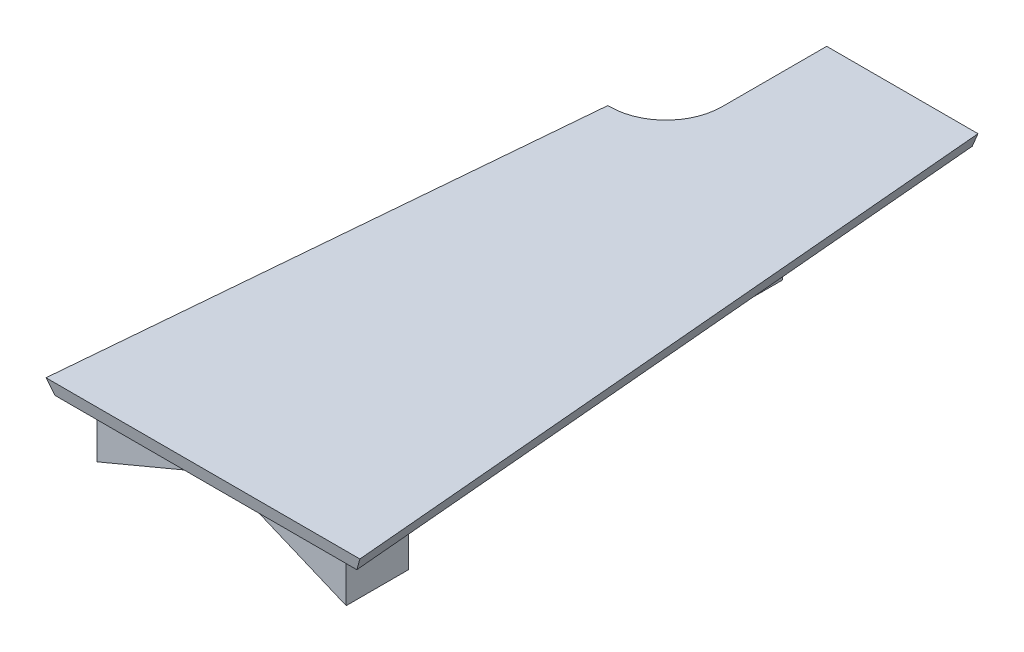
SolidWorks part; units mm, degrees
ref_plane "Ebene vorne" through (0, 0, 0) normal (0, 0, 1) x (1, 0, 0)
ref_plane "Ebene oben" through (0, 0, 0) normal (0, 1, 0) x (1, 0, 0)
ref_plane "Ebene rechts" through (0, 0, 0) normal (1, 0, 0) x (0, 0, -1)
sketch "Skizze1" plane through (0, 0, 0) normal (0, 1, 0) x (1, 0, 0)
  line L1 (-28.5, -61.5) -> (28.5, -61.5)
  line L2 (-28.5, -61.5) -> (-28.5, 61.5)
  line L3 (-28.5, 61.5) -> (28.5, 61.5)
  line L4 (28.5, -61.5) -> (28.5, 61.5)
  line L5 (-28.5, -61.5) -> (28.5, 61.5) construction
  line L6 (-28.5, 61.5) -> (28.5, -61.5) construction
  point P0 (0, 0)
  dimension "D1" = 57
  dimension "D2" = 123
extrude "Aufsatz-Linear austragen1" add sketch "Skizze1" along normal blind 2.5
sketch "Skizze2" plane through (28.5, 0, 0) normal (1, 0, 0) x (0, 0, -1)
  line L0 (-61.5, 2.5) -> (-61.5, 0)
  line L1 (55, 0) -> (-55, 0) construction
  line L2 (-61.5, 2.5) -> (-61.5, 0) construction
  line L3 (-61.5, 0) -> (-60.9686, 0)
  line L4 (-60.9686, 0) -> (-61.5, 2.5)
  dimension "D1" = 102
extrude "Schnitt-Linear austragen1" cut sketch "Skizze2" against normal through all
sketch "Skizze3" plane through (0, 2.5, 0) normal (0, 1, 0) x (1, 0, 0)
  line L0 (-28.5, -61.5) -> (-17.7389, 61.5)
  line L1 (28.5, 61.5) -> (-28.5, 61.5) construction
  line L2 (-17.7389, 61.5) -> (-28.5, 61.5)
  line L3 (-28.5, 61.5) -> (-28.5, -61.5)
  line L4 (28.5, -61.5) -> (17.7389, 61.5)
  line L5 (17.7389, 61.5) -> (28.5, 61.5)
  line L6 (28.5, 61.5) -> (28.5, -61.5)
  dimension "D1" = 95
  dimension "D2" = 95
extrude "Schnitt-Linear austragen2" cut sketch "Skizze3" against normal through all
ref_axis "Achse1" through (23.1194, 2.5, 0) along (0, -1, 0)
ref_plane "Ebene1" through (0.1756, 0, 2.0073) normal (0.0872, 0, 0.9962) x (0, -1, 0)
sketch "Skizze5" plane through (0.1756, 0, 2.0073) normal (0.0872, 0, 0.9962) x (0, -1, 0)
  line L0 (0.0086, 23.0315) -> (-2.5, 23.0315)
  line L1 (-2.5, 23.0315) -> (0, 23.0315) construction
  line L5 (0.0086, 23.0315) -> (0, 21.9959)
  line L6 (0, -33.659) -> (0, 23.0315) construction
  line L7 (0, 21.9959) -> (-2.5, 23.0315)
  line L8 (-2.5, -33.7516) -> (-2.5, 23.0315) construction
  dimension "D1" = 67.5
extrude "Schnitt-Linear austragen3" cut sketch "Skizze5" against normal through all and the other way through all
ref_axis "Achse2" through (-23.0962, -8.4274, -0.2657) along (0, 1, 0)
ref_plane "Ebene2" through (-0.1524, 0, 1.7416) normal (-0.0872, 0, 0.9962) x (0, 1, 0)
sketch "Skizze6" plane through (-0.1524, 0, 1.7416) normal (-0.0872, 0, 0.9962) x (0, 1, 0)
  line L1 (2.5, 23.0315) -> (0, 21.9959)
  line L2 (0, -55) -> (0, 55) construction
  line L3 (0, 21.9959) -> (0, 23.0315)
  line L4 (0, 23.0315) -> (2.5, 23.0315)
  line L5 (2.5, 23.0315) -> (2.5, -33.7516) construction
  dimension "D1" = 67.5
extrude "Schnitt-Linear austragen4" cut sketch "Skizze6" against normal through all and the other way through all
sketch "Skizze9" plane through (0, 0, 0) normal (0, -1, 0) x (1, 0, 0)
  line L6 (0, -61.5) -> (0, 60.9686) construction
  line L11 (16.6994, -61.5) -> (-16.6994, -61.5) construction
  line L12 (-27.414, 60.9686) -> (27.414, 60.9686) construction
  line L13 (0, 52.4686) -> (-26.6704, 52.4686) construction
  line L14 (-16.6994, -61.5) -> (-27.414, 60.9686) construction
  line L15 (-26.6704, 52.4686) -> (26.6704, 52.4686) construction
  line L16 (16.6994, -61.5) -> (27.414, 60.9686) construction
  line L17 (0, -19.5) -> (-20.3739, -19.5) construction
  line L18 (-20.3739, -19.5) -> (20.3739, -19.5) construction
  line L20 (22.6207, 58.1089) -> (-22.6207, 58.1089)
  line L21 (22.6207, 58.1089) -> (22.6207, 46.8283)
  line L22 (22.6207, 46.8283) -> (-22.6207, 46.8283)
  line L23 (-22.6207, 58.1089) -> (-22.6207, 46.8283)
  line L24 (22.6207, 58.1089) -> (-22.6207, 46.8283) construction
  line L25 (22.6207, 46.8283) -> (-22.6207, 58.1089) construction
  dimension "D1" = 42
  dimension "D2" = 8.5
extrude "Aufsatz-Linear austragen2" add sketch "Skizze9" along normal blind 13 contours L21 L20 L23 L22
sketch "Skizze11" plane through (0, 0, 46.8283) normal (0, 0, -1) x (-1, 0, 0)
  line L0 (-22.6207, -9.484) -> (0, 0)
  line L1 (-22.6207, -13) -> (-22.6207, 0) construction
  line L2 (-22.6207, 0) -> (22.6207, 0) construction
  line L3 (0, 0) -> (22.6207, -9.484)
  line L4 (22.6207, -13) -> (22.6207, 0) construction
  line L5 (22.6207, -9.484) -> (22.6207, -13)
  line L6 (22.6207, -13) -> (-22.6207, -13)
  line L7 (-22.6207, -13) -> (-22.6207, -9.484)
extrude "Schnitt-Linear austragen5" cut sketch "Skizze11" against normal blind 20
sketch "Skizze12" plane through (0, 0, 0) normal (0, -1, 0) x (1, 0, 0)
  line L0 (0, -61.5) -> (0, -2.1503) construction
  line L5 (16.6994, -61.5) -> (-16.6994, -61.5) construction
  line L6 (-20.3739, -19.5) -> (20.3739, -19.5) construction
  line L12 (-16.6994, -61.5) -> (-27.414, 60.9686) construction
  line L13 (16.6994, -61.5) -> (27.414, 60.9686) construction
  line L15 (18.0118, -15.2638) -> (-18.0118, -15.2638)
  line L16 (18.0118, -15.2638) -> (18.0118, -25.7362)
  line L17 (18.0118, -25.7362) -> (-18.0118, -25.7362)
  line L18 (-18.0118, -15.2638) -> (-18.0118, -25.7362)
  line L19 (18.0118, -15.2638) -> (-18.0118, -25.7362) construction
  line L24 (18.0118, -25.7362) -> (-18.0118, -15.2638) construction
  point P10 (0, -20.5)
  dimension "D2" = 41
extrude "Aufsatz-Linear austragen3" add sketch "Skizze12" along normal blind 5
sketch "Skizze13" plane through (0, 0, -25.7362) normal (0, 0, -1) x (-1, 0, 0)
  line L0 (-18.0118, -2.5) -> (-7.1831, 0)
  line L3 (-18.0118, -5) -> (-18.0118, 0) construction
  line L4 (18.0118, 0) -> (-18.0118, 0) construction
  line L5 (-7.1831, 0) -> (7.1831, 0)
  line L6 (7.1831, 0) -> (18.0118, -2.5)
  line L7 (18.0118, -5) -> (18.0118, 0) construction
  line L8 (18.0118, -2.5) -> (18.0118, -5)
  line L9 (18.0118, -5) -> (-18.0118, -5)
  line L10 (-18.0118, -5) -> (-18.0118, -2.5)
  dimension "D1" = 103
  dimension "D2" = 103
extrude "Schnitt-Linear austragen6" cut sketch "Skizze13" against normal blind 12
sketch "Skizze16" plane through (0, 0, 0) normal (0, -1, 0) x (1, 0, 0)
  line L0 (7.1831, -25.7362) -> (18.0118, -15.2638) construction
  line L1 (18.0118, -15.2638) -> (-18.0118, -15.2638) construction
  line L2 (-18.0118, -15.2638) -> (-7.1831, -25.7362) construction
  circle A0 centre (12.5975, -20.5) radius 3.1
  circle A1 centre (-12.5975, -20.5) radius 3.1
  dimension "D1" = 6.2
  dimension "D2" = 6.2
extrude "Schnitt-Linear austragen8" cut sketch "Skizze16" against normal blind 1.65 and the other way blind 0.5
ref_plane "Ebene7" through (0, -4.742, 0) normal (0, 1, 0) x (1, 0, 0)
sketch "Skizze17" plane through (0, -4.742, 0) normal (0, 1, 0) x (1, 0, 0)
  line L0 (22.6207, -58.1089) -> (11.3104, -46.8283) construction
  line L1 (0, -46.8283) -> (22.6207, -46.8283) construction
  line L2 (11.3104, -46.8283) -> (-11.3104, -58.1089) construction
  line L3 (-22.6207, -58.1089) -> (0, -58.1089) construction
  line L4 (-11.3104, -58.1089) -> (-22.6207, -46.8283) construction
  circle A0 centre (-16.9656, -52.4686) radius 3.1
  circle A1 centre (16.9656, -52.4686) radius 3.1
  dimension "D1" = 6.2
  dimension "D2" = 6.2
extrude "Schnitt-Linear austragen9" cut sketch "Skizze17" against normal blind 1 and the other way blind 1.15
sketch "Skizze18" plane through (0, 2.5, 0) normal (0, 1, 0) x (1, 0, 0)
  line L0 (-9.7389, 61.5) -> (-9.7389, 42.49)
  line L2 (-19.9121, 32.3168) -> (-20.2921, 32.3168)
  line L4 (-20.2921, 32.3168) -> (-17.7389, 61.5)
  line L5 (-17.7389, 61.5) -> (-9.7389, 61.5)
  line L6 (17.7389, 61.5) -> (-17.7389, 61.5) construction
  line L7 (-28.5, -61.5) -> (-17.7389, 61.5) construction
  arc A0 (-19.9121, 32.3168) -> (-9.7389, 42.49) centre (-19.9121, 42.49) ccw
  point P9 (-19.8952, 42.51)
  dimension "D1" = 8
  dimension "D2" = 19.01
  dimension "D3" = 0
  dimension "D4" = 0
  dimension "D5" = 0.38
extrude "Schnitt-Linear austragen10" cut sketch "Skizze18" against normal blind 10
